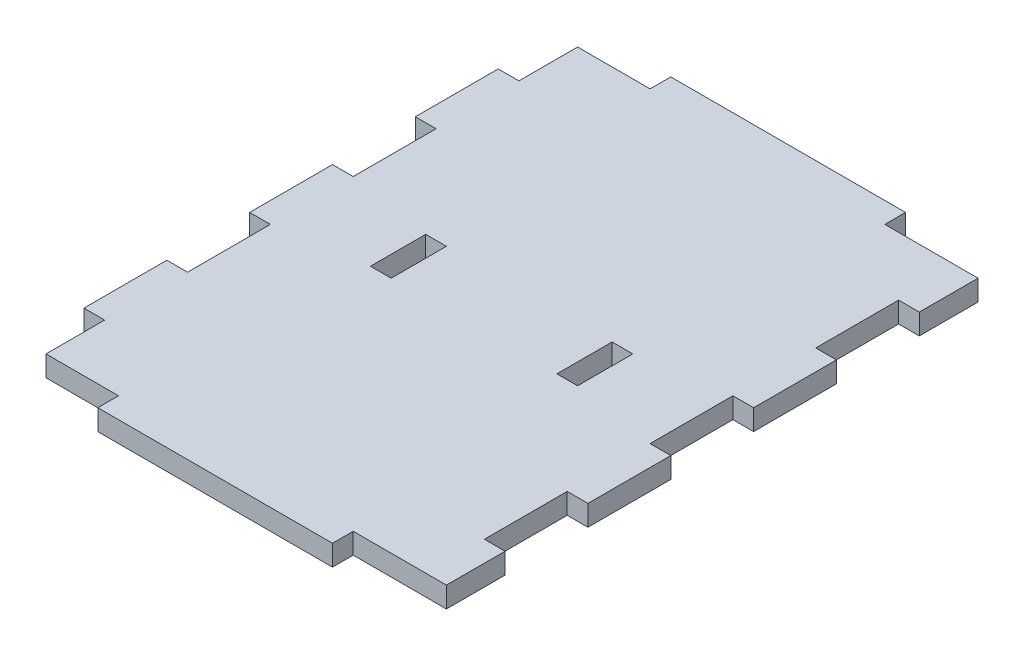
SolidWorks part; units mm, degrees
ref_plane "Alzado" through (0, 0, 0) normal (0, 0, 1) x (1, 0, 0)
ref_plane "Planta" through (0, 0, 0) normal (0, 1, 0) x (1, 0, 0)
ref_plane "Vista lateral" through (0, 0, 0) normal (1, 0, 0) x (0, 0, -1)
sketch "Croquis1" plane through (0, 0, 0) normal (0, 1, 0) x (1, 0, 0)
  line L0 (13.5, 0) -> (47.5, 0)
  line L1 (30.5, 0) -> (13.5, 0)
  line L2 (30.5, 0) -> (47.5, 0)
  line L3 (47.5, 0) -> (47.5, 3)
  line L4 (58, 35.5) -> (58, 47.5)
  line L5 (13.5, 3) -> (13.5, 0)
  line L6 (61, 3) -> (61, 11.5)
  line L7 (0, 11.5) -> (0, 23.5)
  line L8 (61, 23.5) -> (61, 35.5)
  line L9 (13.5, 80) -> (13.5, 83)
  line L10 (58, 47.5) -> (61, 47.5)
  line L11 (47.5, 83) -> (47.5, 80)
  line L12 (13.5, 83) -> (47.5, 83)
  line L13 (13.5, 80) -> (3, 80)
  line L14 (47.5, 80) -> (61, 80)
  line L15 (13.5, 3) -> (3, 3)
  line L16 (47.5, 3) -> (61, 3)
  line L17 (61, 47.5) -> (61, 59.5)
  line L18 (61, 59.5) -> (58, 59.5)
  line L19 (58, 59.5) -> (58, 71.5)
  line L20 (58, 71.5) -> (61, 71.5)
  line L21 (58, 11.5) -> (61, 11.5)
  line L22 (58, 23.5) -> (58, 11.5)
  line L23 (61, 23.5) -> (58, 23.5)
  line L24 (58, 35.5) -> (61, 35.5)
  line L26 (3, 35.5) -> (0, 35.5)
  line L27 (0, 23.5) -> (3, 23.5)
  line L29 (3, 11.5) -> (0, 11.5)
  line L30 (3, 71.5) -> (0, 71.5)
  line L31 (3, 11.5) -> (3, 3)
  line L32 (0, 59.5) -> (3, 59.5)
  line L33 (3, 47.5) -> (0, 47.5)
  line L36 (3, 80) -> (3, 71.5)
  line L37 (61, 71.5) -> (61, 80)
  line L38 (61, 47.5) -> (61, 59.5)
  line L39 (0, 59.5) -> (0, 71.5)
  line L40 (0, 35.5) -> (0, 47.5)
  line L41 (3, 59.5) -> (3, 47.5)
  line L42 (3, 35.5) -> (3, 23.5)
  dimension "D3" = 17
  dimension "D4" = 3
  dimension "D5" = 12
  dimension "D6" = 12
extrude "Saliente-Extruir1" add sketch "Croquis1" along normal blind 3 contours L26 L42 L27 L7 L29 L31 L15 L5 L0 L3 L16 L6 L21 L22 L23 L8 L24 L4 L10 L17 L18 L19 L20 L37 L14 L11 L12 L9 L13 L36 L30 L39 L32 L41 L33 L40 region at (30.5931, 0, -41.5)
sketch "Croquis2" plane through (0, 3, 0) normal (0, 1, 0) x (1, 0, 0)
  line L0 (42.5, 41.5) -> (18.5, 41.5) construction
  line L1 (18.5, 41.5) -> (18.5, 45.5)
  line L2 (18.5, 45.5) -> (15.5, 45.5)
  line L3 (15.5, 45.5) -> (15.5, 37.5)
  line L4 (15.5, 37.5) -> (18.5, 37.5)
  line L5 (18.5, 37.5) -> (18.5, 41.5)
  line L6 (42.5, 37.5) -> (42.5, 41.5)
  line L7 (30.5, 83) -> (30.5, 0) construction
  line L8 (45.5, 37.5) -> (42.5, 37.5)
  line L9 (45.5, 45.5) -> (45.5, 37.5)
  line L10 (42.5, 45.5) -> (45.5, 45.5)
  line L11 (42.5, 41.5) -> (42.5, 45.5)
  line L13 (13.5, 83) -> (47.5, 83) construction
  line L15 (13.5, 0) -> (47.5, 0) construction
  point P17 (30.5, 41.5)
  dimension "D1" = 12
  dimension "D2" = 4
  dimension "D3" = 3
  dimension "D4" = 8
extrude "Cortar-Extruir1" cut sketch "Croquis2" against normal blind 10
